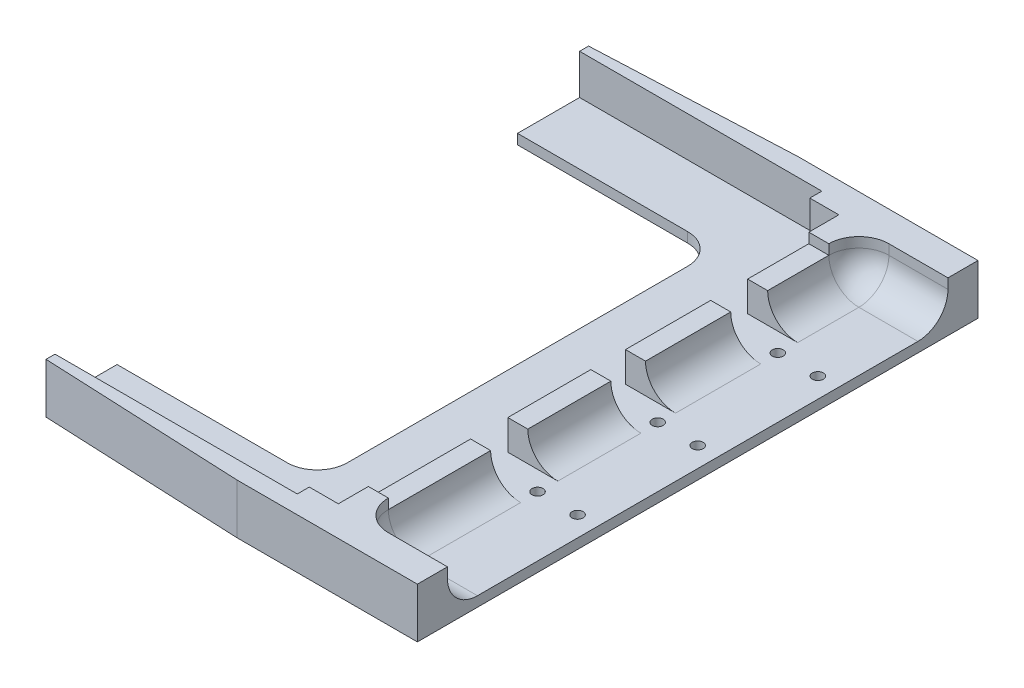
SolidWorks part; units mm, degrees
ref_plane "Front Plane" through (0, 0, 0) normal (0, 0, 1) x (1, 0, 0)
ref_plane "Top Plane" through (0, 0, 0) normal (0, 1, 0) x (1, 0, 0)
ref_plane "Right Plane" through (0, 0, 0) normal (1, 0, 0) x (0, 0, -1)
sketch "profile" plane through (0, 0, 0) normal (0, 0, 1) x (1, 0, 0)
  line L0 (11.8803, 7.4874) -> (14.5, 7.4874)
  line L1 (-5.5, 6.9749) -> (-7.8749, 4.6)
  line L2 (-7.8749, 4.6) -> (-12.1251, 4.6)
  line L3 (-12.1251, 4.6) -> (-14.5, 6.9749)
  line L4 (-8.1197, 7.4874) -> (-5.5, 7.4874)
  line L5 (-14.5, 6.9749) -> (-15.0126, 7.4874)
  line L6 (14.5, 6.9749) -> (12.1251, 4.6)
  line L7 (12.1251, 4.6) -> (7.8749, 4.6)
  line L8 (7.8749, 4.6) -> (5.5, 6.9749)
  line L9 (-14.7464, 10.3536) -> (-5.2536, 10.3536)
  line L10 (-14.5, 7.4874) -> (-11.8803, 7.4874)
  line L11 (5.5, 7.4874) -> (8.5334, 7.4874)
  line L12 (5.6673, 10.3536) -> (14.7464, 10.3536)
  line L13 (-15.0126, 7.4874) -> (-14.5, 7.4874)
  line L14 (-5.5, 6.9749) -> (-4.9874, 7.4874)
  line L15 (-4.9874, 7.4874) -> (-5.5, 7.4874)
  line L16 (5.5, 6.9749) -> (4.9874, 7.4874)
  line L17 (4.9874, 7.4874) -> (5.5, 7.4874)
  line L18 (14.5, 6.9749) -> (15.0126, 7.4874)
  line L19 (15.0126, 7.4874) -> (14.5, 7.4874)
  line L20 (-12.7464, 8.3536) -> (-14.7464, 10.3536)
  line L21 (-5.2536, 10.3536) -> (-7.2536, 8.3536)
  line L22 (7.6673, 8.3536) -> (5.6673, 10.3536)
  line L23 (14.7464, 10.3536) -> (12.7464, 8.3536)
  line L24 (-12.7464, 8.3536) -> (-11.8803, 7.4874)
  line L25 (-7.2536, 8.3536) -> (-8.1197, 7.4874)
  line L26 (7.6673, 8.3536) -> (8.5334, 7.4874)
  line L27 (12.7464, 8.3536) -> (11.8803, 7.4874)
  line L28 (-14.7464, 10.3536) -> (-20, 10.3536)
  line L29 (-20, 10.3536) -> (-20, 15.3536)
  line L30 (-20, 15.3536) -> (20, 15.3536)
  line L31 (20, 15.3536) -> (20, 10.3536)
  line L32 (20, 10.3536) -> (14.7464, 10.3536)
  line L33 (-5.2536, 10.3536) -> (5.6673, 10.3536)
  point P0 (-10, 4.6)
  point P1 (10, 4.6)
  dimension "D1" = 4.2503
  dimension "D2" = 5.7536
  dimension "D3" = 15.7497
  dimension "D4" = 20
  dimension "D5" = 5
extrude "Boss-Extrude1" add sketch "profile" along normal blind 250 contours L9 L33 L12 L32 L31 L30 L29 L28 region at (0, 12.8536, 0)
extrude "Boss-Extrude2" add sketch "Sketch1<3>" along normal blind 50 separate body contours L25 L21 L9 L20 L24 L10 L13 L5 L3 L2 L1 L14 L15 L4 | L27 L23 L12 L22 L26 L11 L17 L16 L8 L7 L6 L18 L19 L0 region at (10.0959, 7.5838, 0) region at (-10, 7.6238, 0)
sketch "Sketch1<3>" plane through (0, 0, 0) normal (0, 0, 1) x (1, 0, 0) same geometry as "profile"
pattern_linear "LPattern1" count 4 spacing 60 along (0, 0, 1) of "Boss-Extrude2"
sketch "Sketch2" plane through (0, 10.3536, 0) normal (0, -1, 0) x (1, 0, 0)
  line L0 (10, 250) -> (10, 0) construction
  line L1 (-20, 250) -> (20, 250) construction
  line L2 (12.1251, 0) -> (7.8749, 0) construction
  line L3 (-10, 230) -> (-10, 0) construction
  line L4 (-7.8749, 230) -> (-12.1251, 230) construction
  line L5 (-7.8749, 0) -> (-12.1251, 0) construction
  line L6 (-7.8749, 180) -> (-7.8749, 170) construction
  line L7 (-7.8749, 180) -> (-12.1251, 180) construction
  circle A0 centre (-10, 175) radius 2.75
  circle A1 centre (10, 175) radius 2.75
  circle A2 centre (-10, 115) radius 2.75
  circle A3 centre (10, 115) radius 2.75
  circle A4 centre (-10, 55) radius 2.75
  circle A5 centre (10, 55) radius 2.75
  point P21 (-7.8749, 175)
  dimension "D1" = 5.5
  dimension "D2" = 3
extrude "Cut-Extrude1" cut sketch "Sketch2" against normal through all
sketch "upper_acrylic_supp" plane through (0, 15.3536, 0) normal (0, 1, 0) x (1, 0, 0)
  line L0 (-20, 0) -> (20, 0) construction
  line L1 (-20, -250) -> (-34.5, -250) construction
  line L2 (-20, -250) -> (-20, 0) construction
  line L3 (-20, 0) -> (-34.5, 0) construction
  line L4 (-34.5, -250) -> (-34.5, 0) construction
  line L6 (-34.5, -250) -> (-24.5, -250)
  line L7 (-34.5, -250) -> (-34.5, -183.9264)
  line L8 (-34.5, -183.9264) -> (-24.5, -183.9264)
  line L9 (-24.5, -250) -> (-24.5, -183.9264)
  line L10 (-34.5, -165.3527) -> (-24.5, -165.3527)
  line L11 (-34.5, -165.3527) -> (-34.5, -123.8775)
  line L12 (-34.5, -123.8775) -> (-24.5, -123.8775)
  line L13 (-24.5, -165.3527) -> (-24.5, -123.8775)
  line L14 (-34.5, -106.5661) -> (-24.5, -106.5661)
  line L15 (-34.5, -106.5661) -> (-34.5, -64.0089)
  line L16 (-34.5, -64.0089) -> (-24.5, -64.0089)
  line L17 (-24.5, -106.5661) -> (-24.5, -64.0089)
  line L18 (-34.5, -45.5583) -> (-24.5, -45.5583)
  line L19 (-34.5, -45.5583) -> (-34.5, 0)
  line L20 (-34.5, 0) -> (-24.5, 0)
  line L21 (-24.5, -45.5583) -> (-24.5, 0)
  line L22 (-20, -250) -> (-40, -250)
  line L23 (-20, -250) -> (-20, 0)
  line L24 (-20, 0) -> (-40, 0)
  line L25 (-40, -250) -> (-40, 0)
  line M21 (-20, 0) -> (-20, -250)
  dimension "D1" = 5.5
  dimension "D2" = 10
  dimension "D3" = 20
extrude "Boss-Extrude3" add sketch "upper_acrylic_supp" against normal blind 5 contours L25 L22 L24 L21 L18 L19 L17 L14 L15 L16 L13 L10 L11 L12 L9 L6 L7 L8 M21 | L14 L17 L16 L15 | L10 L13 L12 L11 | L6 L9 L8 L7 | L18 L21 L20 L19 region at (-29.5, 15.3536, 216.9632) region at (-30.3215, 15.3536, 123.2164) region at (-29.5, 15.3536, 22.7792) region at (-29.5, 15.3536, 144.6151) region at (-29.5, 15.3536, 85.2875)
extrude "Boss-Extrude4" add sketch "upper_acrylic_supp<3>" along normal blind 15 contours L6 L9 L8 L7 | L10 L13 L12 L11 | L14 L17 L16 L15 | L18 L21 L20 L19 region at (-29.5, 15.3536, 216.9632) region at (-29.5, 15.3536, 22.7792) region at (-29.5, 15.3536, 144.6151) region at (-29.5, 15.3536, 85.2875)
sketch "upper_acrylic_supp<3>" plane through (0, 15.3536, 0) normal (0, 1, 0) x (1, 0, 0) same geometry as "upper_acrylic_supp"
fillet "Fillet1" radius 15 4 edges at (-24.5, 15.3536, 22.7792) (-24.5, 15.3536, 85.2875) (-24.5, 15.3536, 144.6151) (-24.5, 15.3536, 216.9632)
sketch "Sketch4" plane through (0, 15.3536, 0) normal (0, 1, 0) x (1, 0, 0)
  line L0 (20, -250) -> (20, 0) construction
  line L1 (-40, -250) -> (20, -250)
  line L2 (-40, -250) -> (-40, -265)
  line L3 (-40, -265) -> (20, -265)
  line L4 (20, -250) -> (20, -265)
  line L5 (-40, 0) -> (20, 0)
  line L6 (-40, 0) -> (-40, 15)
  line L7 (-40, 15) -> (20, 15)
  line L8 (20, 0) -> (20, 15)
  line L10 (-34.5, -265) -> (-34.5, 15) construction
  dimension "D1" = 15
  dimension "D2" = 15
extrude "Boss-Extrude5" add sketch "Sketch4" along normal mid plane 10
extrude "Boss-Extrude6" add sketch "Sketch4<3>" along normal blind 60
sketch "Sketch4<3>" plane through (0, 15.3536, 0) normal (0, 1, 0) x (1, 0, 0) same geometry as "Sketch4"
sketch "Sketch5" plane through (0, 0, 250) normal (0, 0, -1) x (-1, 0, 0)
  line L0 (-20, 75.3536) -> (40, 75.3536) construction
  line L1 (40, 15.3536) -> (34.5, 15.3536)
  line L2 (40, 15.3536) -> (40, 75.3536)
  line L3 (40, 75.3536) -> (34.5, 75.3536)
  line L4 (34.5, 15.3536) -> (34.5, 75.3536)
  line L6 (34.5, 15.3536) -> (24.5, 15.3536)
  line L7 (34.5, 15.3536) -> (34.5, 75.3536)
  line L8 (34.5, 75.3536) -> (24.5, 75.3536)
  line L9 (24.5, 15.3536) -> (24.5, 75.3536)
  line M5 (40, 75.3536) -> (-20, 75.3536)
  line M9 (24.5, 30.3536) -> (34.5, 30.3536)
  dimension "D1" = 5.5
  dimension "D2" = 10
extrude "Boss-Extrude7" add sketch "Sketch5" along normal blind 15 contours L9 L4 M9 M5 region at (-29.5, 52.8536, 250)
extrude "Boss-Extrude8" add sketch "Sketch5<3>" against normal blind 15 from surface contours L9 L4 M9 M5 region at (-29.5, 52.8536, 250) starting at face at (-18.2633, 33.7152, 0)
sketch "Sketch5<3>" plane through (0, 0, 250) normal (0, 0, -1) x (-1, 0, 0) same geometry as "Sketch5"
fillet "Fillet2" radius 15 6 edges at (5.25, 15.3536, 0) (-20.1066, 19.747, 0) (5.25, 15.3536, 250) (-20.1066, 19.747, 250) (-24.5, 52.8536, 0) (-24.5, 52.8536, 250)
sketch "Sketch6" plane through (-40, 0, 0) normal (-1, 0, 0) x (0, 0, 1)
  line L1 (250, 15.3536) -> (256, 15.3536)
  line L2 (250, 15.3536) -> (250, 75.3536)
  line L3 (250, 75.3536) -> (256, 75.3536)
  line L4 (256, 15.3536) -> (256, 75.3536)
  line L6 (0, 15.3536) -> (-6, 15.3536)
  line L7 (0, 15.3536) -> (0, 75.3536)
  line L8 (0, 75.3536) -> (-6, 75.3536)
  line L9 (-6, 15.3536) -> (-6, 75.3536)
  dimension "D1" = 6
  dimension "D2" = 6
extrude "Cut-Extrude2" cut sketch "Sketch6" against normal blind 6
sketch "Sketch7" plane through (-40, 0, 0) normal (-1, 0, 0) x (0, 0, 1)
  line L8 (265, 75.3536) -> (256, 75.3536)
  line L9 (256, 75.3536) -> (256, 15.3536)
  line L10 (256, 15.3536) -> (-6, 15.3536)
  line L11 (-6, 15.3536) -> (-6, 75.3536)
  line L12 (-6, 75.3536) -> (-15, 75.3536)
  line L13 (-15, 75.3536) -> (-15, 10.3536)
  line L14 (-15, 10.3536) -> (265, 10.3536)
  line L15 (265, 10.3536) -> (265, 75.3536)
  line L16 (265, 75.3536) -> (256, 75.3536)
  line L17 (256, 75.3536) -> (256, 15.3536)
  line L18 (256, 15.3536) -> (-6, 15.3536)
  line L19 (-6, 15.3536) -> (-6, 75.3536)
  line L20 (-6, 75.3536) -> (-15, 75.3536)
  line L21 (-15, 75.3536) -> (-15, 10.3536)
  line L22 (-15, 10.3536) -> (265, 10.3536)
  line L23 (265, 10.3536) -> (265, 75.3536)
  dimension "D1" = 0
extrude "Boss-Extrude9" add sketch "Sketch7" along normal blind 30
sketch "Sketch8" plane through (-70, 0, 0) normal (-1, 0, 0) x (0, 0, 1)
  line L0 (-15, 10.3536) -> (265, 10.3536) construction
  line L1 (-44.3745, 35.3536) -> (289.2282, 35.3536)
  line L2 (-44.3745, 35.3536) -> (-44.3745, 94.3849)
  line L3 (-44.3745, 94.3849) -> (289.2282, 94.3849)
  line L4 (289.2282, 35.3536) -> (289.2282, 94.3849)
  dimension "D1" = 25
extrude "Cut-Extrude3" cut sketch "Sketch8" against normal blind 150
sketch "Sketch9" plane through (-34, 0, 0) normal (-1, 0, 0) x (0, 0, 1)
  line L4 (256, 15.3536) -> (256, 35.3536)
  line L5 (256, 35.3536) -> (250, 35.3536)
  line L6 (250, 35.3536) -> (250, 15.3536)
  line L7 (250, 15.3536) -> (256, 15.3536)
  line L8 (256, 15.3536) -> (256, 35.3536)
  line L9 (256, 35.3536) -> (250, 35.3536)
  line L10 (250, 35.3536) -> (250, 15.3536)
  line L11 (250, 15.3536) -> (256, 15.3536)
  line L12 (0, 35.3536) -> (-6, 35.3536)
  line L13 (-6, 35.3536) -> (-6, 15.3536)
  line L14 (-6, 15.3536) -> (0, 15.3536)
  line L15 (0, 15.3536) -> (0, 35.3536)
  line L16 (0, 35.3536) -> (-6, 35.3536)
  line L17 (-6, 35.3536) -> (-6, 15.3536)
  line L18 (-6, 15.3536) -> (0, 15.3536)
  line L19 (0, 15.3536) -> (0, 35.3536)
  dimension "D1" = 0
  dimension "D2" = 0
extrude "cloth_escape_gap" add sketch "Sketch9" along normal blind 15
sketch "Sketch11" plane through (-70, 0, 0) normal (-1, 0, 0) x (0, 0, 1)
  line L0 (256, 35.3536) -> (256, 15.3536) construction
  line L1 (-15, 35.3536) -> (-6, 35.3536)
  line L2 (-15, 35.3536) -> (-15, 15.3536)
  line L3 (-15, 15.3536) -> (-6, 15.3536)
  line L4 (-6, 35.3536) -> (-6, 15.3536)
  line L5 (265, 35.3536) -> (256, 35.3536)
  line L6 (265, 35.3536) -> (265, 15.3536)
  line L7 (265, 15.3536) -> (256, 15.3536)
  line L8 (256, 35.3536) -> (256, 15.3536)
  line L9 (256, 15.3536) -> (256, 35.3536) construction
extrude "Boss-Extrude11" add sketch "Sketch11" along normal blind 100
sketch "Sketch12" plane through (0, 10.3536, 0) normal (0, -1, 0) x (1, 0, 0)
  line L0 (-70, -15) -> (-170, -10.5)
  line L1 (-170, -15) -> (-170, -6) construction
  line L2 (-170, -10.5) -> (-170, -15)
  line L3 (-170, -15) -> (-70, -15) construction
  line L4 (-170, -15) -> (-70, -15)
  line L5 (-70, 265) -> (-170, 260.5)
  line L6 (-170, 256) -> (-170, 265) construction
  line L7 (-170, 260.5) -> (-170, 265)
  line L8 (-170, 265) -> (-70, 265)
  point P13 (-70, 263.6543)
  point P17 (-70.5786, 265)
extrude "Cut-Extrude4" cut sketch "Sketch12" against normal blind 68 contours L8 L7 L5 | L0 L2 L4 region at (-136.6667, 10.3536, 263.5)
sketch "Sketch13" plane through (-70, 0, 0) normal (-1, 0, 0) x (0, 0, 1)
  line L0 (256, 15.3536) -> (265, 15.3536) construction
  line L1 (-15, 10.3536) -> (25, 10.3536)
  line L2 (-15, 10.3536) -> (-15, 15.3536)
  line L3 (-15, 15.3536) -> (25, 15.3536)
  line L4 (25, 10.3536) -> (25, 15.3536)
  line L5 (265, 10.3536) -> (225, 10.3536)
  line L6 (265, 10.3536) -> (265, 15.3536)
  line L7 (265, 15.3536) -> (225, 15.3536)
  line L8 (225, 10.3536) -> (225, 15.3536)
  line L9 (256, 15.3536) -> (-6, 15.3536) construction
  dimension "D1" = 40
  dimension "D2" = 40
extrude "Boss-Extrude13" add sketch "Sketch13" along normal blind 100
sketch "Sketch14" plane through (0, 15.3536, 0) normal (0, 1, 0) x (1, 0, 0)
  line L3 (-70, -265) -> (-170, -260.5)
  line L4 (-170, -260.5) -> (-170, -265)
  line L5 (-170, -265) -> (-70, -265)
  line L6 (-70, -265) -> (-170, -260.5)
  line L7 (-170, -260.5) -> (-170, -265)
  line L8 (-170, -265) -> (-70, -265)
  line L9 (-170, 15) -> (-170, 10.5)
  line L10 (-170, 10.5) -> (-70, 15)
  line L11 (-70, 15) -> (-170, 15)
  line L12 (-170, 15) -> (-170, 10.5)
  line L13 (-170, 10.5) -> (-70, 15)
  line L14 (-70, 15) -> (-170, 15)
  dimension "D1" = 0
  dimension "D2" = 0
extrude "Cut-Extrude5" cut sketch "Sketch14" against normal blind 100
fillet "Fillet3" radius 15 2 edges at (-70, 12.8536, 25) (-70, 12.8536, 225)
